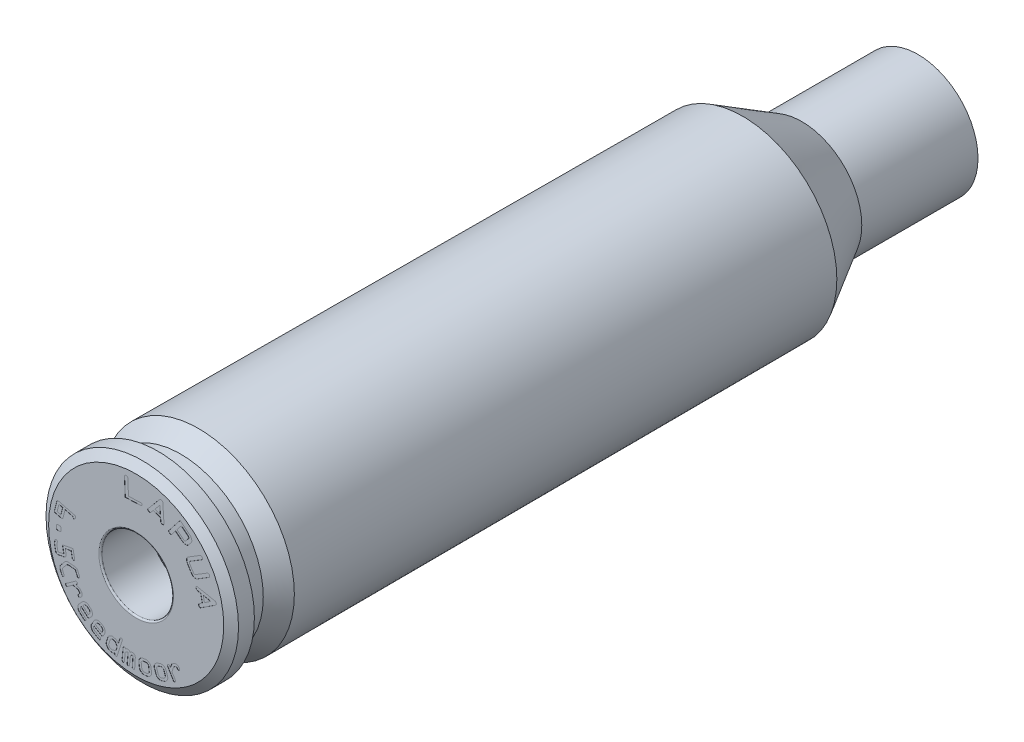
SolidWorks part; units mm, degrees
ref_plane "Front Plane" through (0, 0, 0) normal (0, 0, 1) x (1, 0, 0)
ref_plane "Top Plane" through (0, 0, 0) normal (0, 1, 0) x (1, 0, 0)
ref_plane "Right Plane" through (0, 0, 0) normal (1, 0, 0) x (0, 0, -1)
sketch "Sketch2" plane through (0, 0, 0) normal (1, 0, 0) x (0, 0, -1)
  line L0 (0, 0) -> (0, 5.4623)
  line L1 (0, 5.4623) -> (0.38, 6.005)
  line L2 (0.38, 6.005) -> (1.37, 6.005)
  line L3 (1.37, 6.005) -> (1.37, 5.159)
  line L4 (1.37, 5.159) -> (2.77, 5.159)
  line L5 (2.77, 5.159) -> (3.8931, 5.975)
  line L6 (3.8931, 5.975) -> (37.84, 5.87)
  line L7 (37.84, 5.87) -> (41.5206, 3.745)
  line L8 (41.5206, 3.745) -> (48.77, 3.745)
  line L9 (48.77, 3.745) -> (48.77, 0)
  line L11 (0, 0) -> (48.77, 0)
  point P3 (0, 0)
  point P14 (4.4337, 0)
  point P15 (11.5645, 0.0404)
  point P16 (11.5645, 0.0497)
  dimension "D1" = 35
  dimension "D2" = 0.38
  dimension "D3" = 1.37
  dimension "D4" = 1.4
  dimension "D5" = 6.005
  dimension "D6" = 5.159
  dimension "D7" = 36
  dimension "D8" = 5.87
  dimension "D9" = 5.975
  dimension "D10" = 37.84
  dimension "D11" = 30
  dimension "D12" = 3.745
  dimension "D13" = 48.77
revolve "case_body" add sketch "Sketch2" angle 360 about L11
sketch "Sketch3" plane through (0, 0, 0) normal (1, 0, 0) x (0, 0, -1)
  line L0 (-4.1304, 0) -> (-0.9462, 0) construction
  line L1 (4.63, 0.36) -> (4.63, 0)
  line L2 (4.63, 0) -> (48.77, 0)
  line L3 (48.77, 0) -> (48.77, 0.36)
  line L11 (48.41, 3.385) -> (48.77, 3.385)
  line L12 (48.77, -3.745) -> (48.77, 3.745) construction
  line L13 (48.77, 3.385) -> (48.77, 0.36)
  line L15 (4.63, 5.6127) -> (4.63, 0.36)
  line L22 (0.36, 5.3488) -> (0.36, 0.36)
  line L23 (0.5674, 5.645) -> (0.36, 5.3488)
  line L24 (1.01, 5.645) -> (0.5674, 5.645)
  line L25 (1.01, 4.799) -> (1.01, 5.645)
  line L26 (2.887, 4.799) -> (1.01, 4.799)
  line L27 (4.0096, 5.6146) -> (2.887, 4.799)
  line L28 (37.743, 5.5103) -> (4.0096, 5.6146)
  line L29 (41.4241, 3.385) -> (37.743, 5.5103)
  line L30 (48.41, 3.385) -> (41.4241, 3.385)
  line L31 (48.41, 0.36) -> (48.41, 3.385)
  line L32 (0.36, 0.36) -> (48.41, 0.36)
  line L39 (37.743, 5.5103) -> (4.63, 5.6127)
  line L40 (41.4241, 3.385) -> (37.743, 5.5103)
  line L41 (48.41, 3.385) -> (41.4241, 3.385)
  dimension "D2" = 44.14
  dimension "D1" = 0.36
revolve "Cut-Revolve1" cut sketch "Sketch3" angle 360 about L0
ref_plane "Plane1" through (0, 0, 0) normal (0, 0, 1) x (1, 0, 0)
sketch "Sketch4" plane through (0, 0, 0) normal (0, 0, 1) x (1, 0, 0)
  circle A0 centre (0, 0) radius 2.225
  dimension "D1" = 4.45
extrude "Cut-Extrude1" cut sketch "Sketch4" against normal blind 3.14
sketch "Sketch5" plane through (0, 0, -3.14) normal (0, 0, 1) x (1, 0, 0)
  circle A0 centre (0, 0) radius 0.75
  dimension "D1" = 1.5
extrude "Cut-Extrude2" cut sketch "Sketch5" against normal up to next
ref_axis "Axis1" through (0, 0, -3.8931) along (0, 0, -1)
ref_plane "Plane2" through (0, 0, 0) normal (0, 0, 1) x (1, 0, 0)
sketch "Sketch6" plane through (0, 0, 0) normal (0, 0, 1) x (1, 0, 0)
  line L0 (-4.2638, 0) -> (7.1063, 0) construction
  line L1 (0, 6.2743) -> (0, -6.8752) construction
  line L2 (0, 0) -> (-6.5403, 2.3805) construction
  line L3 (0, 0) -> (7.7907, -1.6292) construction
  arc A0 (-4.8864, 1.7785) -> (0, 5.2) centre (0, 0) ccw construction
  circle A2 centre (0, 0) radius 3.9623
  circle A3 centre (0, 0) radius 3.9623 construction
  text T0 "LAPUA" font "OCR A Extended" height 1.2
  text T1 "6.5Creedmoor" font "OCR A Extended" height 1.2
  dimension "D2" = 160
  dimension "D3" = 5.2
  dimension "D1" = 1.5
extrude "Cut-Extrude3" cut sketch "Sketch6" against normal blind 0.01
fillet "Fillet1" radius 0.1 1 edges at (2.225, 0, 0)
